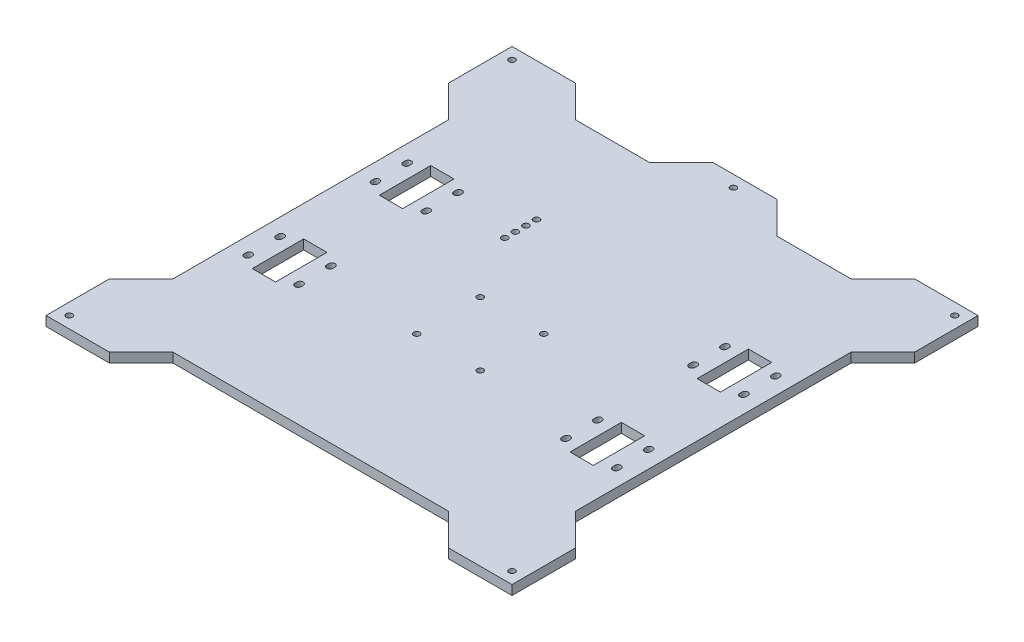
SolidWorks part; units mm, degrees
ref_plane "Front Plane" through (0, 0, 0) normal (0, 0, 1) x (1, 0, 0)
ref_plane "Top Plane" through (0, 0, 0) normal (0, 1, 0) x (1, 0, 0)
ref_plane "Right Plane" through (0, 0, 0) normal (1, 0, 0) x (0, 0, -1)
sketch "Sketch1" plane through (0, 0, 0) normal (0, 1, 0) x (1, 0, 0)
  line L1 (-110, 110) -> (110, 110)
  line L2 (-110, 110) -> (-110, -110)
  line L3 (-110, -110) -> (110, -110)
  line L4 (110, 110) -> (110, -110)
  line L5 (-110, 110) -> (110, -110) construction
  line L6 (-110, -110) -> (110, 110) construction
  point P0 (0, 0)
  dimension "D1" = 220
  dimension "D2" = 220
extrude "Square" add sketch "Sketch1" along normal blind 4.5
sketch "Sketch2" plane through (0, 4.5, 0) normal (0, 1, 0) x (1, 0, 0)
  line L0 (0, 110) -> (0, -110) construction
  line L1 (110, 110) -> (-110, 110) construction
  line L2 (-110, -110) -> (110, -110) construction
  line L3 (-110, 0) -> (110, 0) construction
  line L4 (-110, 110) -> (-110, -110) construction
  line L5 (110, -110) -> (110, 110) construction
  line L6 (75, 110) -> (75, -110) construction
  line L7 (75, 30) -> (0, 30) construction
  line L8 (75, -30) -> (0, -30) construction
  circle A0 centre (87, 38) radius 1.45
  circle A1 centre (87, 22) radius 1.45
  circle A2 centre (63, 22) radius 1.45
  circle A3 centre (63, 38) radius 1.45
  circle A4 centre (-63, 38) radius 1.45
  circle A5 centre (-63, 22) radius 1.45
  circle A6 centre (-87, 22) radius 1.45
  circle A7 centre (-87, 38) radius 1.45
  circle A8 centre (-87, 22) radius 1.45
  circle A9 centre (-87, 38) radius 1.45
  circle A10 centre (-63, 38) radius 1.45
  circle A11 centre (-63, 22) radius 1.45
  circle A12 centre (63, 22) radius 1.45
  circle A13 centre (63, 38) radius 1.45
  circle A14 centre (87, 38) radius 1.45
  circle A15 centre (87, 22) radius 1.45
  circle A16 centre (87, -22) radius 1.45
  circle A17 centre (87, -38) radius 1.45
  circle A18 centre (63, -38) radius 1.45
  circle A19 centre (63, -22) radius 1.45
  circle A20 centre (-63, -22) radius 1.45
  circle A21 centre (-63, -38) radius 1.45
  circle A22 centre (-87, -38) radius 1.45
  circle A23 centre (-87, -22) radius 1.45
  circle A24 centre (-87, -38) radius 1.45
  circle A25 centre (-87, -22) radius 1.45
  circle A26 centre (-63, -22) radius 1.45
  circle A27 centre (-63, -38) radius 1.45
  circle A28 centre (63, -38) radius 1.45
  circle A29 centre (63, -22) radius 1.45
  circle A30 centre (87, -22) radius 1.45
  circle A31 centre (87, -38) radius 1.45
  dimension "D6" = 2.9
  dimension "D7" = 2.9
  dimension "D1" = 75
  dimension "D2" = 30
  dimension "D3" = 16
  dimension "D5" = 12
extrude "LM8UU-Holders" cut sketch "Sketch2" against normal through all contours A7 | A6 | A5 | A4 | A20 | A21 | A22 | A23 | A19 | A18 | A17 | A16 | A1 | A0 | A3 | A2 region at (87, 4.5, -38) region at (87, 4.5, -22) region at (63, 4.5, -22) region at (63, 4.5, -38) region at (-63, 4.5, -38) region at (-63, 4.5, -22) region at (-87, 4.5, -22) region at (-87, 4.5, -38) region at (87, 4.5, 22) region at (87, 4.5, 38) region at (63, 4.5, 38) region at (63, 4.5, 22) region at (-63, 4.5, 22) region at (-63, 4.5, 38) region at (-87, 4.5, 38) region at (-87, 4.5, 22)
sketch "Sketch10" plane through (0, 4.5, 0) normal (0, 1, 0) x (1, 0, 0)
  line L0 (0, 110) -> (0, -79.9796) construction
  line L3 (-26.5242, 0) -> (110, 0) construction
  line L6 (75, 110) -> (75, -110) construction
  line L7 (75, 30) -> (-75, 30) construction
  line L8 (87, 22) -> (87, 23) construction
  line L9 (110, 110) -> (-110, 110) construction
  line L10 (110, -110) -> (110, 110) construction
  line L11 (85.55, 22) -> (85.55, 23)
  line L12 (88.45, 22) -> (88.45, 23)
  line L13 (87, 38) -> (87, 37) construction
  line L14 (88.45, 38) -> (88.45, 37)
  line L15 (85.55, 38) -> (85.55, 37)
  line L16 (63, 38) -> (63, 37) construction
  line L17 (61.55, 38) -> (61.55, 37)
  line L18 (64.45, 38) -> (64.45, 37)
  line L19 (63, 22) -> (63, 23) construction
  line L20 (64.45, 22) -> (64.45, 23)
  line L21 (61.55, 22) -> (61.55, 23)
  line L22 (75, -30) -> (-75, -30) construction
  line L23 (87, -22) -> (87, -23) construction
  line L24 (85.55, -22) -> (85.55, -23)
  line L25 (88.45, -22) -> (88.45, -23)
  line L26 (87, -38) -> (87, -37) construction
  line L27 (88.45, -38) -> (88.45, -37)
  line L28 (85.55, -38) -> (85.55, -37)
  line L29 (63, -38) -> (63, -37) construction
  line L30 (61.55, -38) -> (61.55, -37)
  line L31 (64.45, -38) -> (64.45, -37)
  line L32 (63, -22) -> (63, -23) construction
  line L33 (64.45, -22) -> (64.45, -23)
  line L34 (61.55, -22) -> (61.55, -23)
  line L35 (26.5242, 0) -> (-110, 0) construction
  line L36 (-87, 22) -> (-87, 23) construction
  line L37 (-85.55, 22) -> (-85.55, 23)
  line L38 (-88.45, 22) -> (-88.45, 23)
  line L39 (-87, 38) -> (-87, 37) construction
  line L40 (-88.45, 38) -> (-88.45, 37)
  line L41 (-85.55, 38) -> (-85.55, 37)
  line L42 (-63, 38) -> (-63, 37) construction
  line L43 (-61.55, 38) -> (-61.55, 37)
  line L44 (-64.45, 38) -> (-64.45, 37)
  line L45 (-63, 22) -> (-63, 23) construction
  line L46 (-64.45, 22) -> (-64.45, 23)
  line L47 (-61.55, 22) -> (-61.55, 23)
  line L48 (-87, -22) -> (-87, -23) construction
  line L49 (-85.55, -22) -> (-85.55, -23)
  line L50 (-88.45, -22) -> (-88.45, -23)
  line L51 (-87, -38) -> (-87, -37) construction
  line L52 (-88.45, -38) -> (-88.45, -37)
  line L53 (-85.55, -38) -> (-85.55, -37)
  line L54 (-63, -38) -> (-63, -37) construction
  line L55 (-61.55, -38) -> (-61.55, -37)
  line L56 (-64.45, -38) -> (-64.45, -37)
  line L57 (-63, -22) -> (-63, -23) construction
  line L58 (-64.45, -22) -> (-64.45, -23)
  line L59 (-61.55, -22) -> (-61.55, -23)
  arc A0 (61.55, 38) -> (64.45, 38) centre (63, 38) cw
  arc A1 (88.45, 38) -> (85.55, 38) centre (87, 38) ccw
  arc A2 (85.55, 22) -> (88.45, 22) centre (87, 22) ccw
  arc A3 (88.45, 23) -> (85.55, 23) centre (87, 23) ccw
  arc A4 (85.55, 37) -> (88.45, 37) centre (87, 37) ccw
  arc A5 (64.45, 37) -> (61.55, 37) centre (63, 37) cw
  arc A6 (64.45, 22) -> (61.55, 22) centre (63, 22) cw
  arc A7 (61.55, 23) -> (64.45, 23) centre (63, 23) cw
  arc A8 (85.55, -22) -> (88.45, -22) centre (87, -22) cw
  arc A9 (88.45, -23) -> (85.55, -23) centre (87, -23) cw
  arc A10 (88.45, -38) -> (85.55, -38) centre (87, -38) cw
  arc A11 (85.55, -37) -> (88.45, -37) centre (87, -37) cw
  arc A12 (61.55, -38) -> (64.45, -38) centre (63, -38) ccw
  arc A13 (64.45, -37) -> (61.55, -37) centre (63, -37) ccw
  arc A14 (64.45, -22) -> (61.55, -22) centre (63, -22) ccw
  arc A15 (61.55, -23) -> (64.45, -23) centre (63, -23) ccw
  arc A16 (-85.55, 22) -> (-88.45, 22) centre (-87, 22) cw
  arc A17 (-88.45, 23) -> (-85.55, 23) centre (-87, 23) cw
  arc A18 (-88.45, 38) -> (-85.55, 38) centre (-87, 38) cw
  arc A19 (-85.55, 37) -> (-88.45, 37) centre (-87, 37) cw
  arc A20 (-61.55, 38) -> (-64.45, 38) centre (-63, 38) ccw
  arc A21 (-64.45, 37) -> (-61.55, 37) centre (-63, 37) ccw
  arc A22 (-64.45, 22) -> (-61.55, 22) centre (-63, 22) ccw
  arc A23 (-61.55, 23) -> (-64.45, 23) centre (-63, 23) ccw
  arc A24 (-85.55, -22) -> (-88.45, -22) centre (-87, -22) ccw
  arc A25 (-88.45, -23) -> (-85.55, -23) centre (-87, -23) ccw
  arc A26 (-88.45, -38) -> (-85.55, -38) centre (-87, -38) ccw
  arc A27 (-85.55, -37) -> (-88.45, -37) centre (-87, -37) ccw
  arc A28 (-61.55, -38) -> (-64.45, -38) centre (-63, -38) cw
  arc A29 (-64.45, -37) -> (-61.55, -37) centre (-63, -37) cw
  arc A30 (-64.45, -22) -> (-61.55, -22) centre (-63, -22) cw
  arc A31 (-61.55, -23) -> (-64.45, -23) centre (-63, -23) cw
  point P8 (87, 22.5)
  point P19 (87, 37.5)
  point P28 (63, 37.5)
  point P35 (63, 22.5)
  point P44 (87, -22.5)
  point P51 (87, -37.5)
  point P58 (63, -37.5)
  point P65 (63, -22.5)
  point P73 (0, 30)
  point P74 (0, -30)
  point P76 (-87, 22.5)
  point P83 (-87, 37.5)
  point P90 (-63, 37.5)
  point P97 (-63, 22.5)
  point P104 (-87, -22.5)
  point P111 (-87, -37.5)
  point P118 (-63, -37.5)
  point P125 (-63, -22.5)
  dimension "D1" = 75
  dimension "D2" = 30
  dimension "D3" = 16
  dimension "D5" = 12
  dimension "D4" = 1.45
  dimension "D7" = 1.45
  dimension "D8" = 1
  dimension "D9" = 1
sketch "Sketch3" plane through (0, 4.5, 0) normal (0, 1, 0) x (1, 0, 0)
  line L0 (0, -110) -> (0, 110) construction
  line L1 (-110, -110) -> (110, -110) construction
  line L2 (110, 110) -> (-110, 110) construction
  line L3 (110, -15) -> (-110, -15) construction
  line L6 (15, -30) -> (-15, -30) construction
  line L7 (15, 0) -> (-15, 0) construction
  line L8 (110, -110) -> (110, 110) construction
  line L9 (-110, 110) -> (-110, -110) construction
  line L10 (110, 0) -> (-110, 0) construction
  circle A0 centre (-15, -30) radius 1.45
  circle A1 centre (15, -30) radius 1.45
  circle A2 centre (15, 0) radius 1.45
  circle A3 centre (-15, 0) radius 1.45
  point P16 (0, -30)
  dimension "D1" = 2.9
  dimension "D2" = 15
  dimension "D3" = 15
  dimension "D5" = 15
extrude "DefaultBelt" cut sketch "Sketch3" against normal through all
sketch "Sketch4" plane through (0, 4.5, 0) normal (0, 1, 0) x (1, 0, 0)
  line L0 (0, 110) -> (0, -110) construction
  line L1 (110, 110) -> (-110, 110) construction
  line L2 (-110, -110) -> (110, -110) construction
  line L3 (-15, -1.45) -> (-15, -28.55) construction
  line L4 (15, -28.55) -> (15, -1.45) construction
  line L5 (15, -15) -> (-15, -15) construction
  arc A0 (-0.7348, 6.25) -> (0.7348, 6.25) centre (0, 5) ccw
  arc A1 (0.7348, 6.25) -> (-0.7348, 6.25) centre (0, 7.5) ccw
  arc A2 (0.7348, -36.25) -> (-0.7348, -36.25) centre (0, -37.5) cw
  arc A3 (-0.7348, -36.25) -> (0.7348, -36.25) centre (0, -35) cw
  circle A4 centre (-15, 0) radius 1.45 construction
  circle A5 centre (-15, -30) radius 1.45 construction
  circle A6 centre (15, -30) radius 1.45 construction
  circle A7 centre (15, 0) radius 1.45 construction
  dimension "D1" = 2.9
  dimension "D2" = 2.9
  dimension "D3" = 20
  dimension "D4" = 22.5
extrude "BeltOptions" [suppressed] cut sketch "Sketch4" against normal through all
sketch "Sketch5" plane through (0, 4.5, 0) normal (0, 1, 0) x (1, 0, 0)
  line L0 (-110, 0) -> (110, 0) construction
  line L1 (-110, 110) -> (-110, -110) construction
  line L2 (110, -110) -> (110, 110) construction
  line L3 (0, 110) -> (0, -110) construction
  line L4 (110, 110) -> (-110, 110) construction
  line L5 (-110, 110) -> (-110, 80)
  line L6 (-110, 80) -> (-95, 65)
  line L7 (-95, 65) -> (-95, -65)
  line L8 (0, 0) -> (-110, 110) construction
  line L9 (-65, 95) -> (65, 95)
  line L10 (-80, 110) -> (-65, 95)
  line L11 (-110, 110) -> (-80, 110)
  line L12 (-95, 65) -> (-95, -65)
  line L13 (0, 0) -> (110, 110) construction
  line L14 (95, 65) -> (95, -65)
  line L15 (110, 110) -> (80, 110)
  line L16 (80, 110) -> (65, 95)
  line L17 (95, 65) -> (95, -65)
  line L18 (110, 80) -> (95, 65)
  line L19 (110, 110) -> (110, 80)
  line L20 (0, 0) -> (110, -110) construction
  line L21 (0, 0) -> (-110, -110) construction
  line L22 (110, -110) -> (110, -80)
  line L23 (110, -80) -> (95, -65)
  line L24 (80, -110) -> (65, -95)
  line L25 (110, -110) -> (80, -110)
  line L26 (-110, -110) -> (-80, -110)
  line L27 (-80, -110) -> (-65, -95)
  line L28 (-65, -95) -> (65, -95)
  line L29 (-110, -80) -> (-95, -65)
  line L30 (-110, -110) -> (-110, -80)
  point P24 (0, 95)
  point P32 (95, 0)
  point P35 (-95, 0)
  point P36 (0, -95)
  circle M16 centre (15, -30) radius 1.45
  circle M18 centre (63, 38) radius 1.45
  circle M20 centre (87, 22) radius 1.45
  circle M22 centre (87, -38) radius 1.45
  circle M23 centre (63, -38) radius 1.45
  circle M24 centre (63, -22) radius 1.45
  circle M25 centre (-87, -22) radius 1.45
  circle M26 centre (-87, -38) radius 1.45
  circle M27 centre (-63, -38) radius 1.45
  circle M28 centre (-63, -22) radius 1.45
  circle M29 centre (-63, 38) radius 1.45
  circle M30 centre (-63, 22) radius 1.45
  circle M31 centre (-87, 22) radius 1.45
  circle M32 centre (-87, 38) radius 1.45
  line M33 (110, -110) -> (110, 110)
  line M34 (110, 110) -> (-110, 110)
  line M35 (-110, 110) -> (-110, -110)
  line M36 (-110, -110) -> (110, -110)
  dimension "D1" = 15
  dimension "D2" = 30
  dimension "D3" = 45
  dimension "D4" = 45
extrude "Shaping" cut sketch "Sketch5" against normal blind 10 flip side to cut contours L29 L27 L28 L24 L23 L14 L18 L16 L9 L10 L6 L7 M35 M36 M33 M34 M16 M18 M20 M22 M24 M26 M28 M30 M32 M31 M29 M27 M25 M23 region at (0.037, 4.5, -0.0113)
sketch "Sketch6" plane through (0, 4.5, 0) normal (0, 1, 0) x (1, 0, 0)
  line L0 (-110, 110) -> (110, -110) construction
  line L1 (-110, -110) -> (110, 110) construction
  line L2 (110, 80) -> (110, 110) construction
  line L3 (0, 95) -> (0, -95) construction
  line L4 (-65, 95) -> (65, 95) construction
  line L5 (-65, -95) -> (65, -95) construction
  line L6 (-95, 0) -> (95, 0) construction
  line L7 (-95, 65) -> (-95, -65) construction
  line L8 (95, 65) -> (95, -65) construction
  circle A0 centre (-104.5, 104.5) radius 1.45
  circle A1 centre (104.5, 104.5) radius 1.45
  circle A2 centre (104.5, -104.5) radius 1.45
  circle A3 centre (-104.5, -104.5) radius 1.45
  dimension "D2" = 2.9
  dimension "D1" = 45
  dimension "D3" = 104.5
extrude "Cut-Extrude5" cut sketch "Sketch6" against normal through all
sketch "Sketch7" plane through (0, 4.5, 0) normal (0, 1, 0) x (1, 0, 0)
  line L0 (-87, 38) -> (-63, 22) construction
  line L1 (-63, 22) -> (-87, 22) construction
  line L2 (-87, 22) -> (-63, 38) construction
  line L3 (-63, 38) -> (-87, 38) construction
  line L4 (-95, 0) -> (95, 0) construction
  line L5 (-80.5, 42.125) -> (-69.5, 42.125)
  line L6 (-80.5, 42.125) -> (-80.5, 17.875)
  line L7 (-80.5, 17.875) -> (-69.5, 17.875)
  line L8 (-69.5, 42.125) -> (-69.5, 17.875)
  line L9 (-80.5, 42.125) -> (-69.5, 17.875) construction
  line L10 (-80.5, 17.875) -> (-69.5, 42.125) construction
  line L11 (-95, 65) -> (-95, -65) construction
  line L12 (95, 65) -> (95, -65) construction
  line L13 (0, -95) -> (0, 95) construction
  line L14 (-65, -95) -> (65, -95) construction
  line L15 (-65, 95) -> (65, 95) construction
  line L16 (-80.5, -17.875) -> (-69.5, -42.125) construction
  line L17 (-80.5, -42.125) -> (-69.5, -17.875) construction
  line L18 (-63, -38) -> (-87, -38) construction
  line L19 (-87, -22) -> (-63, -38) construction
  line L20 (-63, -22) -> (-87, -22) construction
  line L21 (-87, -38) -> (-63, -22) construction
  line L22 (-69.5, -42.125) -> (-69.5, -17.875)
  line L23 (-80.5, -17.875) -> (-69.5, -17.875)
  line L24 (-80.5, -42.125) -> (-80.5, -17.875)
  line L25 (-80.5, -42.125) -> (-69.5, -42.125)
  line L26 (-80.5, 17.875) -> (-69.5, 42.125) construction
  line L27 (80.5, 17.875) -> (69.5, 42.125) construction
  line L28 (87, -38) -> (63, -22) construction
  line L29 (63, -22) -> (87, -22) construction
  line L30 (87, -22) -> (63, -38) construction
  line L31 (63, -38) -> (87, -38) construction
  line L32 (80.5, -42.125) -> (69.5, -17.875) construction
  line L33 (80.5, -17.875) -> (69.5, -42.125) construction
  line L34 (80.5, 17.875) -> (69.5, 42.125) construction
  line L35 (80.5, 42.125) -> (69.5, 17.875) construction
  line L36 (63, 38) -> (87, 38) construction
  line L37 (87, 22) -> (63, 38) construction
  line L38 (63, 22) -> (87, 22) construction
  line L39 (87, 38) -> (63, 22) construction
  line L40 (80.5, -42.125) -> (69.5, -42.125)
  line L41 (80.5, -42.125) -> (80.5, -17.875)
  line L42 (80.5, -17.875) -> (69.5, -17.875)
  line L43 (69.5, -42.125) -> (69.5, -17.875)
  line L44 (69.5, 42.125) -> (69.5, 17.875)
  line L45 (80.5, 17.875) -> (69.5, 17.875)
  line L46 (80.5, 42.125) -> (80.5, 17.875)
  line L47 (80.5, 42.125) -> (69.5, 42.125)
  point P4 (-75, 30)
  point P33 (-75, -30)
  point P50 (75, -30)
  point P51 (75, 30)
  dimension "D1" = 11
  dimension "D2" = 24.25
extrude "Cut-Extrude6" cut sketch "Sketch7" against normal through all
sketch "Sketch8" plane through (0, 4.5, 0) normal (0, 1, 0) x (1, 0, 0)
  line L3 (-65, 95) -> (65, 95) construction
  line L4 (-33.45, 45) -> (-33.45, 30) construction
  circle A0 centre (-33.45, 45) radius 1.45
  circle A1 centre (-33.45, 40) radius 1.45
  circle A2 centre (-33.45, 35) radius 1.45
  circle A3 centre (-33.45, 30) radius 1.45
  dimension "D1" = 2.9
  dimension "D2" = 50
  dimension "D4" = 33.45
extrude "EndstopTrigger" cut sketch "Sketch8" against normal through all
pattern_linear "LPattern1" [suppressed] count 2 spacing 30 of bodies 108
sketch "Sketch9" plane through (0, 4.5, 0) normal (0, 1, 0) x (1, 0, 0)
  line L0 (-80, 110) -> (-110, 110) construction
  line L1 (-65, 95) -> (65, 95) construction
  line L7 (-95, 0) -> (95, 0) construction
  line L8 (-95, 65) -> (-95, -65) construction
  line L11 (95, 65) -> (95, -65) construction
  line L12 (-104.5, 104.5) -> (104.5, 104.5) construction
  line L13 (0, 110) -> (0, 95) construction
  line L14 (-80, 110) -> (80, 110) construction
  line L15 (15, 110) -> (30, 95)
  line L16 (-30, 95) -> (30, 95)
  line L17 (-15, 110) -> (-30, 95)
  line L18 (15, 110) -> (-15, 110)
  circle A1 centre (0, 104.5) radius 1.45
  dimension "D2" = 30
  dimension "D3" = 2.9
  dimension "D1" = 45
  dimension "D4" = 45
extrude "Boss-Extrude1" add sketch "Sketch9" against normal through all
extrude "HolesToSlots" cut sketch "Sketch10" against normal through all
sketch "Sketch11" plane through (0, 4.5, 0) normal (0, 1, 0) x (1, 0, 0)
  line L0 (0, -95) -> (0, 0) construction
  line L1 (-65, -95) -> (65, -95) construction
  line L2 (95, 0) -> (0, 0) construction
  line L3 (95, 65) -> (95, -65) construction
  line L4 (0, 0) -> (110, -110) construction
  line L5 (-69.1421, -85) -> (-5, -85)
  line L6 (-69.1421, -85) -> (-84.1421, -100)
  line L7 (-84.1421, -100) -> (-100, -100)
  line L8 (-100, -100) -> (-100, -84.1421)
  line L9 (-100, -84.1421) -> (-85, -69.1421)
  line L10 (-85, -69.1421) -> (-85, -52.125)
  line L11 (-85, -52.125) -> (-5, -52.125)
  line L12 (-80, -110) -> (-65, -95) construction
  line L13 (-110, -80) -> (-95, -65) construction
  line L14 (-110, -80) -> (-110, -110) construction
  line L15 (-110, -110) -> (-80, -110) construction
  line L16 (-80.5, -42.125) -> (-69.5, -42.125) construction
  line L17 (-95, 65) -> (-95, -65) construction
  line L18 (-5, -52.125) -> (-5, -85)
  line L19 (5, -52.125) -> (5, -85)
  line L20 (85, -52.125) -> (5, -52.125)
  line L21 (85, -69.1421) -> (85, -52.125)
  line L22 (100, -84.1421) -> (85, -69.1421)
  line L23 (100, -100) -> (100, -84.1421)
  line L24 (84.1421, -100) -> (100, -100)
  line L25 (69.1421, -85) -> (84.1421, -100)
  line L26 (69.1421, -85) -> (5, -85)
  line L27 (69.1421, 85) -> (5, 85)
  line L28 (69.1421, 85) -> (84.1421, 100)
  line L29 (84.1421, 100) -> (100, 100)
  line L30 (100, 100) -> (100, 84.1421)
  line L31 (100, 84.1421) -> (85, 69.1421)
  line L32 (85, 69.1421) -> (85, 52.125)
  line L33 (85, 52.125) -> (5, 52.125)
  line L34 (5, 52.125) -> (5, 85)
  line L35 (-5, 52.125) -> (-5, 85)
  line L36 (-85, 52.125) -> (-5, 52.125)
  line L37 (-85, 69.1421) -> (-85, 52.125)
  line L38 (-100, 84.1421) -> (-85, 69.1421)
  line L39 (-100, 100) -> (-100, 84.1421)
  line L40 (-84.1421, 100) -> (-100, 100)
  line L41 (-69.1421, 85) -> (-84.1421, 100)
  line L42 (-69.1421, 85) -> (-5, 85)
  dimension "D1" = 10
  dimension "D2" = 10
  dimension "D3" = 10
  dimension "D4" = 10
  dimension "D5" = 10
  dimension "D6" = 10
  dimension "D7" = 10
  dimension "D8" = 5
extrude "Cut-Extrude7" [suppressed] cut sketch "Sketch11" against normal through all
sketch "Sketch12" [suppressed] plane through (0, 4.5, 0) normal (0, 1, 0) x (1, 0, 0)
  line L0 (0, 0) -> (-110, -110) construction
  line L1 (-110, -110) -> (-80, -110) construction
  line L2 (-110, -80) -> (80, 110) construction
  line L3 (110, 80) -> (-80, -110) construction
  line L4 (-95, -65) -> (-65, -95) construction
  line L5 (0, 0) -> (0, -95) construction
  line L6 (-65, -95) -> (65, -95) construction
  line L7 (95, 0) -> (-95, 0) construction
  line L8 (-95, 65) -> (-95, -65) construction
  line L9 (-100, -100) -> (-100, -84.1421)
  line L10 (-100, -84.1421) -> (-59.2893, -43.4315)
  line L11 (-59.2893, -43.4315) -> (-43.4315, -43.4315)
  line L12 (-110, -80) -> (-110, -110) construction
  line L13 (-100, -100) -> (-84.1421, -100)
  line L14 (-84.1421, -100) -> (-43.4315, -59.2893)
  line L15 (-43.4315, -59.2893) -> (-43.4315, -43.4315)
  line L16 (55, -85) -> (-55, -85)
  line L17 (-55, -85) -> (-29.2893, -59.2893)
  line L18 (-29.2893, -59.2893) -> (29.2893, -59.2893)
  line L19 (95, -65) -> (65, -95) construction
  line L20 (0, 0) -> (110, -110) construction
  line L21 (55, -85) -> (29.2893, -59.2893)
  line L22 (43.4315, -59.2893) -> (43.4315, -43.4315)
  line L23 (84.1421, -100) -> (43.4315, -59.2893)
  line L24 (100, -100) -> (84.1421, -100)
  line L25 (59.2893, -43.4315) -> (43.4315, -43.4315)
  line L26 (100, -84.1421) -> (59.2893, -43.4315)
  line L27 (100, -100) -> (100, -84.1421)
  line L28 (95, 65) -> (65, 95) construction
  line L29 (-95, 65) -> (-65, 95) construction
  line L30 (100, 100) -> (100, 84.1421)
  line L31 (100, 84.1421) -> (59.2893, 43.4315)
  line L32 (59.2893, 43.4315) -> (43.4315, 43.4315)
  line L33 (100, 100) -> (84.1421, 100)
  line L34 (84.1421, 100) -> (43.4315, 59.2893)
  line L35 (43.4315, 59.2893) -> (43.4315, 43.4315)
  line L36 (55, 85) -> (29.2893, 59.2893)
  line L37 (-29.2893, 59.2893) -> (29.2893, 59.2893)
  line L38 (-55, 85) -> (-29.2893, 59.2893)
  line L39 (55, 85) -> (-55, 85)
  line L40 (-43.4315, 59.2893) -> (-43.4315, 43.4315)
  line L41 (-84.1421, 100) -> (-43.4315, 59.2893)
  line L42 (-100, 100) -> (-84.1421, 100)
  line L43 (-59.2893, 43.4315) -> (-43.4315, 43.4315)
  line L44 (-100, 84.1421) -> (-59.2893, 43.4315)
  line L45 (-100, 100) -> (-100, 84.1421)
  point P40 (0, -59.2893)
  point P41 (0, -85)
  point P67 (0, 85)
  point P68 (0, 59.2893)
  dimension "D1" = 10
  dimension "D2" = 10
  dimension "D3" = 80
  dimension "D4" = 10
  dimension "D5" = 10
  dimension "D6" = 0
extrude "Cut-Extrude8" [suppressed] cut sketch "Sketch12" against normal through all
sketch "Sketch14" [suppressed] plane through (0, 4.5, 0) normal (0, 1, 0) x (1, 0, 0)
  line L0 (0, 85) -> (0, 110) construction
  line L1 (55, 85) -> (-55, 85) construction
  line L2 (15, 110) -> (-15, 110) construction
  line L3 (10.8579, 100) -> (-10.8579, 100)
  line L4 (-10.8579, 100) -> (-25.8579, 85)
  line L5 (-25.8579, 85) -> (25.8579, 85)
  line L6 (-15, 110) -> (-30, 95) construction
  line L7 (10.8579, 100) -> (25.8579, 85)
  point P13 (0, 100)
  dimension "D1" = 10
  dimension "D2" = 10
extrude "Cut-Extrude10" [suppressed] cut sketch "Sketch14" against normal through all
sketch "Sketch13" [suppressed] plane through (0, 4.5, 0) normal (0, 1, 0) x (1, 0, 0)
  line L0 (-59.2893, 43.4315) -> (-59.2893, -43.4315) construction
  line L1 (-100, 84.1421) -> (-59.2893, 43.4315) construction
  line L2 (-59.2893, 0) -> (0, 0) construction
  line L3 (-59.2893, 33.4315) -> (-59.2893, -33.4315)
  line L4 (-59.2893, -33.4315) -> (-43.4315, -33.4315)
  line L5 (-43.4315, -33.4315) -> (-43.4315, 33.4315)
  line L6 (-43.4315, 33.4315) -> (-59.2893, 33.4315)
  line L7 (-59.2893, 43.4315) -> (-43.4315, 43.4315) construction
  line L8 (-43.4315, -43.4315) -> (-59.2893, -43.4315) construction
  line L9 (-43.4315, 43.4315) -> (-43.4315, 59.2893) construction
  line L10 (0, 0) -> (0, 43.4315) construction
  line L11 (59.2893, 43.4315) -> (59.2893, -43.4315) construction
  line L12 (43.4315, 33.4315) -> (59.2893, 33.4315)
  line L13 (43.4315, -33.4315) -> (43.4315, 33.4315)
  line L14 (59.2893, -33.4315) -> (43.4315, -33.4315)
  line L15 (59.2893, 33.4315) -> (59.2893, -33.4315)
  line L16 (110, -110) -> (0, 0) construction
  line L17 (55, -85) -> (29.2893, -59.2893) construction
  line L18 (-33.4315, -43.2893) -> (33.4315, -43.2893)
  line L19 (-33.4315, -43.2893) -> (-33.4315, -63.4315)
  line L20 (-33.4315, -63.4315) -> (33.4315, -63.4315)
  line L21 (33.4315, -43.2893) -> (33.4315, -63.4315)
  line L22 (-33.4315, -43.2893) -> (33.4315, -63.4315) construction
  line L23 (-33.4315, -63.4315) -> (33.4315, -43.2893) construction
  line L24 (-43.4315, -59.2893) -> (-43.4315, -43.4315) construction
  line L25 (0, -53.3604) -> (0, -63.4315) construction
  line L26 (55, 85) -> (25.8579, 85) construction
  line L28 (43.4315, -43.4315) -> (43.4315, -59.2893) construction
  line L29 (29.2893, -59.2893) -> (-29.2893, -59.2893) construction
  line L30 (43.4315, 59.2893) -> (43.4315, 43.4315) construction
  line L31 (-33.4315, 83) -> (33.4315, 83)
  line L32 (-33.4315, 83) -> (-33.4315, 15)
  line L33 (-33.4315, 15) -> (33.4315, 15)
  line L34 (33.4315, 83) -> (33.4315, 15)
  line L35 (-33.4315, 83) -> (33.4315, 15) construction
  line L36 (-33.4315, 15) -> (33.4315, 83) construction
  point P27 (0, -53.3604)
  point P43 (0, 49)
  point P50 (0, 0)
  dimension "D1" = 10
  dimension "D2" = 10
  dimension "D3" = 10
  dimension "D4" = 10
  dimension "D5" = 16
  dimension "D6" = 10
  dimension "D7" = 10
  dimension "D8" = 15
  dimension "D9" = 2
extrude "Cut-Extrude9" [suppressed] cut sketch "Sketch13" against normal through all
sketch "Sketch15" [suppressed] plane through (0, 4.5, 0) normal (0, 1, 0) x (1, 0, 0)
  line L0 (-59.2893, 0) -> (-95, 0) construction
  line L1 (-59.2893, 33.4315) -> (-59.2893, -33.4315) construction
  line L2 (-95, 65) -> (-95, -65) construction
  line L3 (-80.5, 17.875) -> (-69.5, 17.875) construction
  line L4 (-59.2893, -15) -> (-59.2893, -7.875)
  line L5 (-85, -7.875) -> (-85, 7.875)
  line L6 (-85, 7.875) -> (-66.4143, 7.875)
  line L7 (-59.2893, -7.875) -> (-59.2893, 7.875)
  line L8 (-66.4143, -7.875) -> (-59.2893, -15)
  line L9 (-85, -7.875) -> (-66.4143, -7.875)
  line L11 (-66.4143, 7.875) -> (-59.2893, 15)
  line L12 (-59.2893, 15) -> (-59.2893, 7.875)
  line L13 (0, 0) -> (0, -21.7485) construction
  line L14 (59.2893, 0) -> (95, 0) construction
  line L15 (59.2893, 15) -> (59.2893, 7.875)
  line L16 (66.4143, 7.875) -> (59.2893, 15)
  line L17 (85, -7.875) -> (66.4143, -7.875)
  line L18 (66.4143, -7.875) -> (59.2893, -15)
  line L19 (59.2893, -7.875) -> (59.2893, 7.875)
  line L20 (85, 7.875) -> (66.4143, 7.875)
  line L21 (85, -7.875) -> (85, 7.875)
  line L22 (59.2893, -15) -> (59.2893, -7.875)
  line L23 (-59.2893, 0) -> (-95, 0) construction
  point P17 (-85, 0)
  point P30 (85, 0)
  dimension "D1" = 10
  dimension "D2" = 10
  dimension "D4" = 45
  dimension "D5" = 15
extrude "Cut-Extrude11" [suppressed] cut sketch "Sketch15" against normal through all
sketch "Sketch16" [suppressed] plane through (0, 4.5, 0) normal (0, 1, 0) x (1, 0, 0)
  line L0 (-85, -69.1421) -> (-85, -52.125)
  line L1 (-59.2893, -43.4315) -> (-100, -84.1421) construction
  line L2 (-85, -52.125) -> (-67.9829, -52.125)
  line L3 (-67.9829, -52.125) -> (-85, -69.1421)
  line L4 (-95, 65) -> (-95, -65) construction
  line L5 (-80.5, -42.125) -> (-69.5, -42.125) construction
  line L6 (-95, 0) -> (95, 0) construction
  line L7 (95, 65) -> (95, -65) construction
  line L8 (0, 0) -> (0, -95) construction
  line L9 (-65, -95) -> (65, -95) construction
  line L10 (-67.9829, 52.125) -> (-85, 69.1421)
  line L11 (-85, 52.125) -> (-67.9829, 52.125)
  line L12 (-85, 69.1421) -> (-85, 52.125)
  line L13 (-67.9829, -52.125) -> (-85, -69.1421)
  line L14 (67.9829, -52.125) -> (85, -69.1421)
  line L15 (85, 69.1421) -> (85, 52.125)
  line L16 (85, 52.125) -> (67.9829, 52.125)
  line L17 (67.9829, 52.125) -> (85, 69.1421)
  line L18 (67.9829, -52.125) -> (85, -69.1421)
  line L19 (85, -52.125) -> (67.9829, -52.125)
  line L20 (85, -69.1421) -> (85, -52.125)
  line L21 (100, -84.1421) -> (59.2893, -43.4315) construction
  line L23 (69.5, -42.125) -> (80.5, -42.125) construction
  line L24 (80.5, 42.125) -> (69.5, 42.125) construction
  line L25 (59.2893, 43.4315) -> (100, 84.1421) construction
  line L26 (-100, 84.1421) -> (-59.2893, 43.4315) construction
  line L27 (-69.5, 42.125) -> (-80.5, 42.125) construction
  dimension "D1" = 10
  dimension "D2" = 10
  dimension "D3" = 10
  dimension "D4" = 10
  dimension "D5" = 10
  dimension "D6" = 10
  dimension "D7" = 10
  dimension "D8" = 10
extrude "Cut-Extrude12" [suppressed] cut sketch "Sketch16" against normal through all contours L3 L2 L0 | L10 L12 L11 | L17 L16 L15 | L14 L20 L19
equation "\"X-ROD-SPACING\"=45"
equation "\"Y-ROD-SPACING\"=75"
equation "\"Z-ROD-SPACING\"=17.5"
equation "\"Y-BED-OFFSET\"=2"
equation "\"Y-BED-ROD-INSET\"=3.5"
equation "\"T-SLOT-NUT-FILLET-RADIUS\"=0.5"
equation "\"T-SLOT-SCREW-SHAFT-RADIUS\"=1.55"
equation "\"T-SLOT-SCREW-SHAFT-CUTOUT-LENGTH\"=11.0"
equation "\"T-SLOT-NUT-DEPTH\"=3.5"
equation "\"T-SLOT-NUT-WIDTH\"=2.85"
equation "\"T-SLOT-NUT-END-DISTANCE\"=8"
equation "\"ACRYLIC-THICKNESS\"=10"
equation "\"ACRYLIC-THICKNESS2\"=4.5"
equation "\"ACRYLIC-TAB-CUTOUT-SIZE\"=\"ACRYLIC-THICKNESS\"+\"ACRYLIC-TAB-TOLERANCE\"*2"
equation "\"ACRYLIC-TAB-WIDTH\"=\"ACRYLIC-THICKNESS\""
equation "\"ACRYLIC-M3-HOLE\"=2.9"
equation "\"SMOOTHROD-CAP-SCREW-DISTANCE\"=20"
equation "\"FRAME-WIDTH-INNER\"=370"
equation "\"NEMA17-HOLE-SPACING\"=31"
equation "\"NEMA17-CENTRAL-CUTOUT\"=22.5"
equation "\"Z-BRACKET-REACH\"=55"
equation "\"TOP-BRACKET-SPACING\"=40"
equation "\"SMOOTHROD-X-LENGTH\"=350"
equation "\"SMOOTHROD-Y-LENGTH\"=350"
equation "\"SMOOTHROD-Z-LENGTH\"=350"
equation "\"SMOOTHROD-TIGHTENING-HEADROOM\"=.25"
equation "\"LEADSCREW-Z-LENGTH\"=300"
equation "\"SCREW-LENGTH-FRAME\"=\"ACRYLIC-THICKNESS\" + 10"
equation "\"SCREW-HEAD-RADIUS\"=6"
equation "\"PRINTED-X-SMOOTHROD-DIAMETER\"=9.0"
equation "\"PRINTED-X-SMOOTHROD-CUTOUT\"=10"
equation "\"PRINTED-X-BASE-HEIGHT\"=10"
equation "\"PRINTED-LM8UU-CUTOUT-SIZE\"=15.5"
equation "\"PRINTED-LM8UU-CUTOUT-LENGTH\"=24.5"
equation "\"PRINTED-X-IDLER-HEIGHT\"=16"
equation "\"PSU-MOUNTING-WIDTH\"=95"
equation "\"PSU-MOUNTING-HEIGHT\"=177"
equation "\"Y-BELT-TO-ROD-DISTANCE\"=20"
equation "\"D6@Sketch2\"=\"ACRYLIC-M3-HOLE\""
equation "\"D7@Sketch2\"=\"ACRYLIC-M3-HOLE\""
equation "\"D1@Sketch2\"=\"Y-ROD-SPACING\""
equation "\"D1@Sketch3\"=\"ACRYLIC-M3-HOLE\""
equation "\"D2@Sketch6\"=\"ACRYLIC-M3-HOLE\""
equation "\"Y-BED-SCREW-SPACING\"=209"
equation "\"Y-BED-SCREW-CUTOUT-SLOT-HEIGHT\"=2"
equation "\"ACRYLIC-TAB-TOLERANCE\"=-.05"
equation "\"Z-ROD-INSET\"=16"
equation "\"SCREW-LENGTH-MOTOR\"=\"ACRYLIC-THICKNESS\" + 5"
equation "\"SCREW-LENGTH-EXTRUDER\"=28"
equation "\"PRINTED-M3-HOLE\"=3.5"
equation "\"SPOOL-HOLDER-ROD-SPACING\"=150"
equation "\"ACRYLIC-X-CARRIAGE-WIDTH\"=55"
equation "\"ACRYLIC-X-CARRIAGE-HEIGHT\"=75"
equation "\"ACRYLIC-X-CARRIAGE-LM8UU-CUTOUT-WIDTH\"=24.25"
equation "\"ACRYLIC-X-CARRIAGE-LM8UU-CUTOUT-HEIGHT\"=11.0"
equation "\"ACRYLIC-X-CARRIAGE-SCREW-SPACING-X\"=15"
equation "\"ACRYLIC-X-CARRIAGE-SCREW-SPACING-Y\"=33"
equation "\"ACRYLIC-X-CARRIAGE-CENTER-TAB-SPACING\"=14"
equation "\"ACRYLIC-X-CARRIAGE-EXTRUDER-OFFSET\"=26"
equation "\"ACRYLIC-X-CARRIAGE-EXTRUDER-ANGLE\"=90"
equation "\"ACRYLIC-X-CARRIAGE-EXTRUDER-SHELF-DEPTH\"=\"ACRYLIC-X-CARRIAGE-EXTRUDER-OFFSET\" + 28"
equation "\"ACRYLIC-X-CARRIAGE-EXTRUDER-BRACE-SPACING\"=23"
equation "\"ACRYLIC-X-CARRIAGE-EXTRUDER-BRACE-TAB-OFFSET\"=20"
equation "\"ACRYLIC-X-CARRIAGE-EXTRUDER-BRACE-HEIGHT\"=35"
equation "\"ACRYLIC-X-CARRIAGE-EXTRUDER-BRACE-SCREW-SPACING\"=22"
equation "\"ACRYLIC-X-CARRIAGE-DUAL-WIDTH-MULTIPLIER\"=1.65"
equation "\"ACRYLIC-X-CARRIAGE-DUAL-HOTEND-SPACING\"=42"
equation "\"ACRYLIC-X-CARRIAGE-DUAL-WIDTH\"=75"
equation "\"ACRYLIC-X-CARRIAGE-DUAL-HOTEND-SEPARATION\"=36"
equation "\"ACRYLIC-X-CARRIAGE-DUAL-MOUNT-PLATE-DEPTH\"=75"
equation "\"ACRYLIC-X-CARRIAGE-DUAL-MOUNT-BRACE-WIDTH\"=33"
equation "\"ACRYLIC-X-CARRIAGE-DUAL-MOUNT-SCREW-WIDTH\"=40"
equation "\"BLOWER-FAN-WIDTH\"=15"
equation "\"D1@Sketch7\"=\"ACRYLIC-X-CARRIAGE-LM8UU-CUTOUT-HEIGHT\""
equation "\"D2@Sketch7\"=\"ACRYLIC-X-CARRIAGE-LM8UU-CUTOUT-WIDTH\""
equation "\"D1@Sketch8\"=\"ACRYLIC-M3-HOLE\""
equation "\"D2@Sketch4\"=\"ACRYLIC-M3-HOLE\""
equation "\"D1@Sketch4\"=\"ACRYLIC-M3-HOLE\""
equation "\"D3@Sketch4\"=20"
equation "\"D3@Sketch9\"=\"ACRYLIC-M3-HOLE\""
equation "\"D4@Sketch10\"=\"ACRYLIC-M3-HOLE\"/2"
equation "\"D7@Sketch10\"=\"ACRYLIC-M3-HOLE\" / 2"
